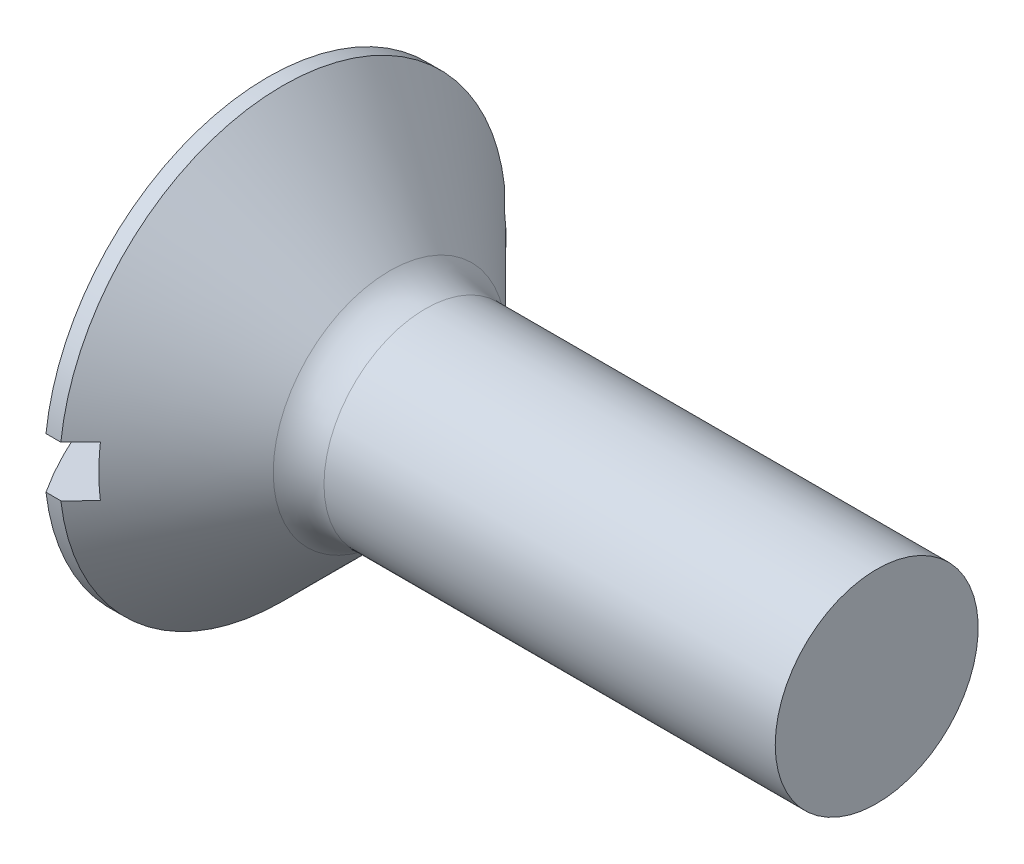
SolidWorks part; units mm, degrees
ref_plane "Front" through (0, 0, 0) normal (0, 0, 1) x (1, 0, 0)
ref_plane "Top" through (0, 0, 0) normal (0, 1, 0) x (1, 0, 0)
ref_plane "Right" through (0, 0, 0) normal (1, 0, 0) x (0, 0, -1)
sketch "Ske-Screw" plane through (0, 0, 0) normal (0, 0, 1) x (1, 0, 0)
  line L0 (0.6593, 2.2) -> (0.8058, 2.2)
  line L1 (0.6593, 0) -> (0, 0)
  line L2 (2.2129, 1) -> (6.6593, 1)
  line L3 (6.6593, 1) -> (6.6593, 0)
  line L4 (6.6593, 0) -> (0.6593, 0)
  line L5 (-1.3499, 0) -> (8.9842, 0) construction
  line L6 (0.8058, 2.2) -> (1.8593, 1.1464)
  arc A0 (0.6593, 2.2) -> (0, 0) centre (4, 0) ccw
  arc A1 (1.8593, 1.1464) -> (2.2129, 1) centre (2.2129, 1.5) ccw
  dimension "D3" = 45
revolve "Base" add sketch "Ske-Screw" angle 360 about L5
cosmetic thread "ThreadCosmetic1" [suppressed] parameters "D1"=4, "D2"=1.567
sketch "Ske-Slot" plane through (0, 0, 0) normal (0, 0, 1) x (1, 0, 0)
  line L1 (-1.3728, 0) -> (2.5237, 0) construction
  line L2 (0, -0.25) -> (1, -0.25)
  line L3 (0, -0.25) -> (0, 0.25)
  line L4 (0, 0.25) -> (1, 0.25)
  line L5 (1, -0.25) -> (1, 0.25)
  arc A0 (0.6593, 2.2) -> (0.6593, -2.2) centre (4, 0) ccw construction
  dimension "n" = 0.5
  dimension "t" = 1
extrude "Slot" cut sketch "Ske-Slot" against normal through all and the other way through all
sketch "Sketch1" plane through (0, 0, 0) normal (0, 0, 1) x (1, 0, 0)
  line L0 (5.8578, 0) -> (-1.624, 0) construction
  line L1 (1.8593, 5.7835) -> (5.6593, 5.7835)
  line L2 (1.8593, 5.7835) -> (1.8593, 0.7835)
  line L3 (1.8593, 0.7835) -> (4.9093, 0.7835)
  line L4 (5.6593, 5.7835) -> (5.6593, 1)
  line L6 (0.6593, 2.2) -> (0.6593, 0.25) construction
  line L7 (6.6593, -1) -> (6.6593, 1) construction
  line L9 (2.2129, 1) -> (6.6593, 1) construction
  line L10 (5.6593, 1) -> (4.9093, 0.7835)
  dimension "b" = 1
  dimension "D4" = 5
  dimension "x" = 0.75
  dimension "D2" = 1.567
sketch "Sketch2" plane through (0, 0, 0) normal (0, 0, 1) x (1, 0, 0)
  line L0 (6.6593, 0.8125) -> (6.7676, 1)
  line L1 (6.7676, 1) -> (6.7676, 1.2165)
  line L2 (6.7676, 1.2165) -> (6.5511, 1.2165)
  line L3 (6.5511, 1.2165) -> (6.5511, 1)
  line L4 (6.5511, 1) -> (6.6593, 0.8125)
  line L5 (0, 0) -> (7.193, 0) construction
  line L6 (6.6593, -1) -> (6.6593, 1) construction
  dimension "D1" = 2
  dimension "D2" = 0.2165
revolve "Cut-Revolve10" [suppressed] cut sketch "Sketch2" angle 360 about L5
pattern_linear "LPattern10" [suppressed] count 14 spacing 0.2598 along (-1, 0, 0) of bodies 104
equation "\"D1@Sketch2\" = \"d@Ske-Screw\""
equation "\"D2@Sketch2\" =  ( \"d@Ske-Screw\" - \"D2@ThreadCosmetic1\" )  / 2"
equation "\"D3@LPattern10\" = \"D2@Sketch2\" * 1.2"
equation "\"D1@LPattern10\" = \"D1@ThreadCosmetic1\" / \"D3@LPattern10\" - 1"
